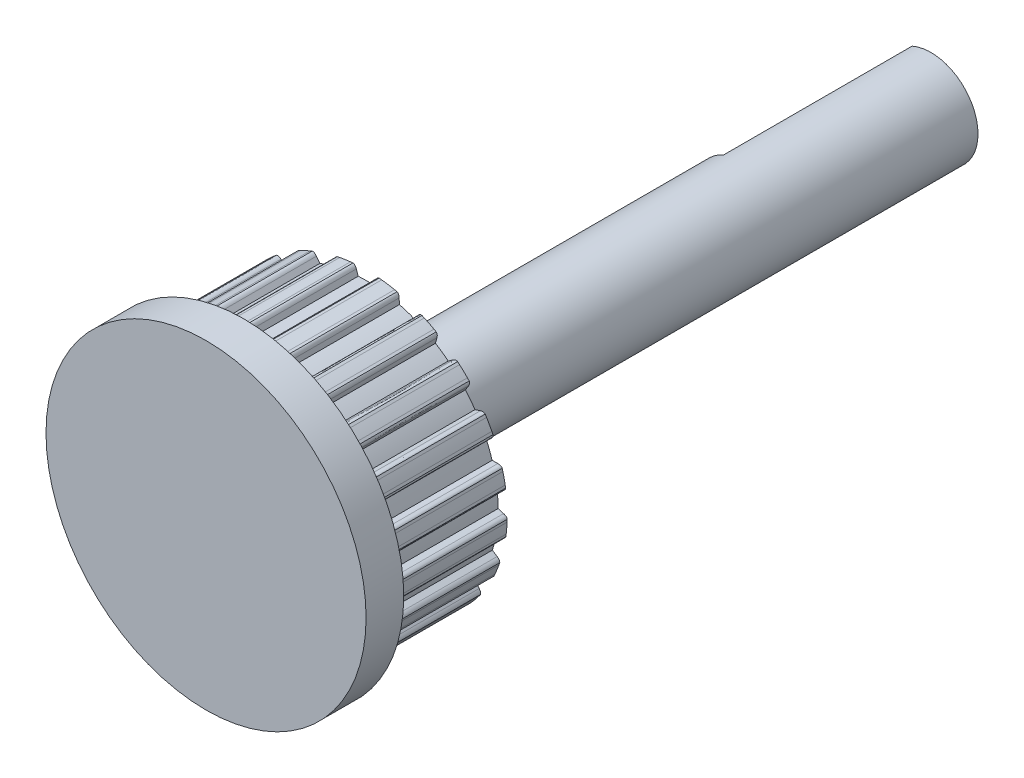
SolidWorks part; units mm, degrees
ref_plane "Plan de face" through (0, 0, 0) normal (0, 0, 1) x (1, 0, 0)
ref_plane "Plan de dessus" through (0, 0, 0) normal (0, 1, 0) x (1, 0, 0)
ref_plane "Plan de droite" through (0, 0, 0) normal (1, 0, 0) x (0, 0, -1)
sketch "Esquisse1" plane through (0, 0, 0) normal (0, 0, 1) x (1, 0, 0)
  line L0 (0, 0) -> (0, 11.7813) construction
  circle A0 centre (0, 0) radius 7.5
  dimension "D1" = 15
extrude "Boss.-Extru.1" add sketch "Esquisse1" along normal blind 6.5 contours A0
sketch "Esquisse2" plane through (0, 0, 6.5) normal (0, 0, 1) x (1, 0, 0)
  line L9 (0, 0) -> (0, 11.354) construction
  line L14 (0.415, 7) -> (0.5183, 7.2837)
  line L15 (0.695, 7.4677) -> (0.83, 7.4539)
  line L16 (-0.83, 7.4539) -> (-0.83, 7.5979)
  line L17 (-0.83, 7.5979) -> (0.83, 7.5979)
  line L18 (0.83, 7.5979) -> (0.83, 7.4539)
  line L22 (-0.415, 7) -> (0.415, 7) construction
  line L23 (0.5183, 7.2837) -> (0.5798, 7.4527) construction
  line L24 (0.5798, 7.4527) -> (0.695, 7.4677) construction
  line L25 (-0.415, 7) -> (-0.5183, 7.2837)
  line L26 (-0.5183, 7.2837) -> (-0.5798, 7.4527) construction
  line L27 (-0.5798, 7.4527) -> (-0.695, 7.4677) construction
  line L28 (-0.695, 7.4677) -> (-0.83, 7.4539)
  circle A0 centre (0, 0) radius 10
  arc A2 (-0.415, 7) -> (0.415, 7) centre (0, 0) cw
  circle A7 centre (0, 0) radius 7.5 construction
  spline S0 degree 2 poles (0.5183, 7.2837) (0.5798, 7.4527) (0.695, 7.4677) knots 0 0 0 1 1 1
  spline S1 degree 2 poles (-0.5183, 7.2837) (-0.5798, 7.4527) (-0.695, 7.4677) knots 0 0 0 1 1 1
  point P11 (0, 7)
  dimension "D1" = 20
  dimension "D9" = 0.135
  dimension "D4" = 0.28
  dimension "D2" = 110
  dimension "D5" = 0.83
  dimension "D6" = 7
extrude "Enlèv. mat.-Extru.1" cut sketch "Esquisse2" against normal up to next contours L17 L18 L15 S0 L14 A2 L25 S1 L28 L16
pattern_circular "Répétition circulaire1" count 21 every 17.1 about axis through (0, 0, 6.5) along (0, 0, 1) of "Enlèv. mat.-Extru.1"
sketch "Esquisse3" plane through (0, 0, 6.5) normal (0, 0, 1) x (1, 0, 0)
  circle A0 centre (0, 0) radius 8.5
  dimension "D1" = 17
extrude "Boss.-Extru.2" add sketch "Esquisse3" along normal blind 2
ref_axis "Axe1" through (0, 0, 8.5) along (0, 0, -1)
sketch "Esquisse4" plane through (0, 0, 0) normal (0, 0, -1) x (-1, 0, 0)
  circle A0 centre (0, 0) radius 2.5
  dimension "D1" = 5
extrude "Boss.-Extru.3" add sketch "Esquisse4" along normal blind 30 contours A0
sketch "Esquisse5" plane through (0, 0, -30) normal (0, 0, -1) x (-1, 0, 0)
  line L0 (2.5, 0) -> (2.5, -6.5828) construction
  line L1 (1, 3.2914) -> (4, 3.2914)
  line L2 (1, 3.2914) -> (1, -3.2914)
  line L3 (1, -3.2914) -> (4, -3.2914)
  line L4 (4, 3.2914) -> (4, -3.2914)
  line L5 (2.5, 0) -> (-4.1983, 0) construction
  point P4 (2.5, -3.2914)
  point P8 (1, 0)
  dimension "D1" = 3
  dimension "D2" = 1
extrude "Enlèv. mat.-Extru.2" cut sketch "Esquisse5" against normal blind 10
